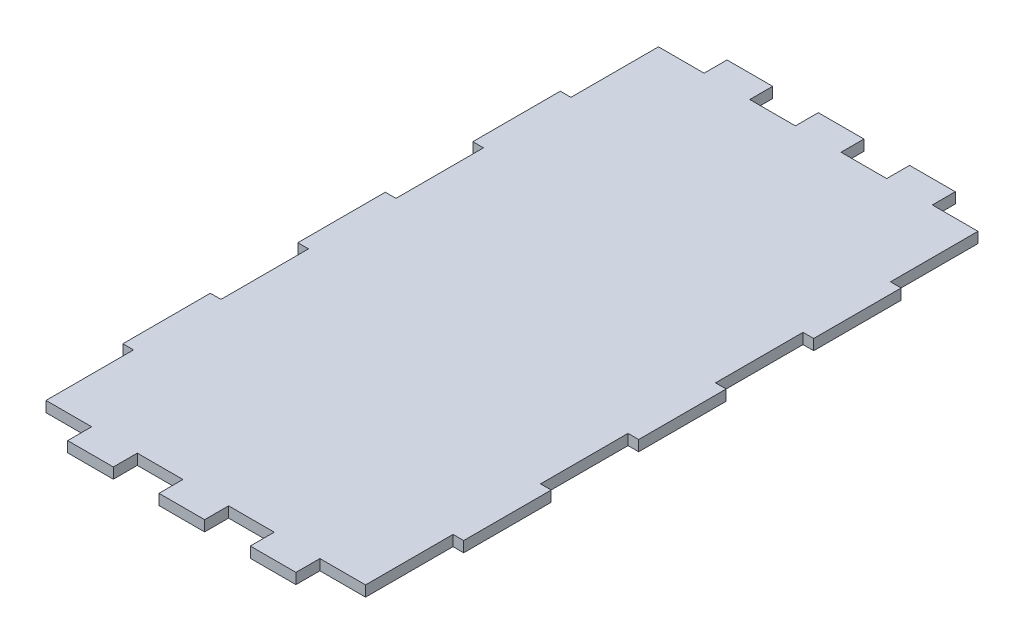
SolidWorks part; units mm, degrees
ref_plane "前视基准面" through (0, 0, 0) normal (0, 0, 1) x (1, 0, 0)
ref_plane "上视基准面" through (0, 0, 0) normal (0, 1, 0) x (1, 0, 0)
ref_plane "右视基准面" through (0, 0, 0) normal (1, 0, 0) x (0, 0, -1)
other "Configuration Table"
sketch "草图4" plane through (0, 0, 0) normal (0, 1, 0) x (1, 0, 0)
  line L6 (-30, -57.5) -> (30, -57.5)
  line L11 (-30, -57.5) -> (-30, 57.5)
  line L12 (-30, 57.5) -> (30, 57.5)
  line L13 (30, -57.5) -> (30, 57.5)
  line L14 (-30, -57.5) -> (30, 57.5) construction
  line L15 (-30, 57.5) -> (30, -57.5) construction
  point P0 (0, 0)
  dimension "D1" = 60
  dimension "D2" = 115
extrude "凸台-拉伸1" add sketch "草图4" along normal blind 2
sketch "草图5" plane through (0, 0, 57.5) normal (0, 0, 1) x (1, 0, 0)
  line L0 (-30, 2) -> (30, 2) construction
  line L1 (21.4286, 2) -> (12.8571, 2)
  line L2 (21.4286, 2) -> (21.4286, 0)
  line L3 (21.4286, 0) -> (12.8571, 0)
  line L4 (12.8571, 2) -> (12.8571, 0)
  line L5 (-30, 0) -> (30, 0) construction
  line L6 (-21.4286, 1) -> (-30, 1)
  line L7 (4.2857, 2) -> (-4.2857, 2)
  line L8 (4.2857, 2) -> (4.2857, 0)
  line L9 (4.2857, 0) -> (-4.2857, 0)
  line L10 (-4.2857, 2) -> (-4.2857, 0)
  line L11 (-12.8571, 2) -> (-21.4286, 2)
  line L12 (-12.8571, 2) -> (-12.8571, 0)
  line L13 (-12.8571, 0) -> (-21.4286, 0)
  line L14 (-21.4286, 2) -> (-21.4286, 0)
  line L15 (-30, 2) -> (-30, 0) construction
  line L16 (-12.8571, 1) -> (-4.2857, 1)
  line L17 (4.2857, 1) -> (12.8571, 1)
  line L18 (21.4286, 1) -> (30, 1)
  line L19 (30, 2) -> (30, 0) construction
extrude "凸台-拉伸2" add sketch "草图5" along normal blind 4.5 contours L1 L4 L3 L2 | L7 L10 L9 L8 | L11 L14 L13 L12
extrude "凸台-拉伸3" add sketch "草图5<3>" against normal blind 4.3 from surface contours L1 L4 L3 L2 | L7 L10 L9 L8 | L11 L14 L13 L12 starting at face at (0, 1, -57.5)
sketch "草图5<3>" plane through (0, 0, 57.5) normal (0, 0, 1) x (1, 0, 0) same geometry as "草图5"
sketch "草图6" plane through (30, 0, 0) normal (1, 0, 0) x (0, 0, -1)
  line L10 (-57.5, 0) -> (-57.5, 2) construction
  line L19 (57.5, 0) -> (57.5, 2) construction
  line L20 (-57.5, 2) -> (57.5, 2) construction
  line L21 (-41.0714, 2) -> (-24.6429, 2)
  line L22 (-41.0714, 2) -> (-41.0714, 0)
  line L23 (-41.0714, 0) -> (-24.6429, 0)
  line L24 (-24.6429, 2) -> (-24.6429, 0)
  line L25 (-57.5, 0) -> (57.5, 0) construction
  line L26 (-57.5, 1) -> (-41.0714, 1) construction
  line L27 (-8.2143, 2) -> (8.2143, 2)
  line L28 (-8.2143, 2) -> (-8.2143, 0)
  line L29 (-8.2143, 0) -> (8.2143, 0)
  line L30 (8.2143, 2) -> (8.2143, 0)
  line L31 (24.6429, 2) -> (41.0714, 2)
  line L32 (24.6429, 2) -> (24.6429, 0)
  line L33 (24.6429, 0) -> (41.0714, 0)
  line L34 (41.0714, 2) -> (41.0714, 0)
  line L35 (-41.0714, 1) -> (-24.6429, 1) construction
  line L36 (-24.6429, 1) -> (-8.2143, 1) construction
  line L37 (-8.2143, 1) -> (8.2143, 1) construction
  line L38 (8.2143, 1) -> (24.6429, 1) construction
  line L39 (24.6429, 1) -> (41.0714, 1) construction
  line L40 (41.0714, 1) -> (57.5, 1) construction
extrude "凸台-拉伸4" add sketch "草图6" along normal blind 2
extrude "凸台-拉伸5" add sketch "草图6<2>" against normal blind 2 from surface starting at face at (-30, 1, 0)
sketch "草图6<2>" plane through (30, 0, 0) normal (1, 0, 0) x (0, 0, -1) same geometry as "草图6"
